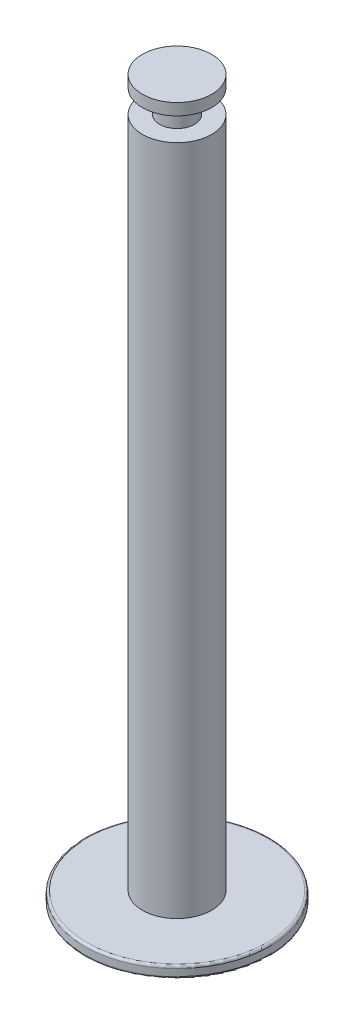
SolidWorks part; units mm, degrees
ref_plane "Front Plane" through (0, 0, 0) normal (0, 0, 1) x (1, 0, 0)
ref_plane "Top Plane" through (0, 0, 0) normal (0, 1, 0) x (1, 0, 0)
ref_plane "Right Plane" through (0, 0, 0) normal (1, 0, 0) x (0, 0, -1)
sketch "Sketch1" plane through (0, 0, 0) normal (0, 1, 0) x (1, 0, 0)
  circle A0 centre (0, 0) radius 7.99
extrude "Boss-Extrude1" add sketch "Sketch1" along normal blind 1
fillet "Fillet1" radius 0.2 2 edges at (0, 0, 7.99) (0, 1, 7.99)
sketch "Sketch2" plane through (0, 1, 0) normal (0, 1, 0) x (1, 0, 0)
  circle A0 centre (0, 0) radius 2.99
extrude "Boss-Extrude3" add sketch "Sketch2" along normal blind 58
sketch "Sketch4" plane through (0, 59, 0) normal (0, 1, 0) x (1, 0, 0)
  circle A0 centre (0, 0) radius 1.5
extrude "Boss-Extrude4" add sketch "Sketch4" along normal blind 2
sketch "Sketch5" plane through (0, 61, 0) normal (0, 1, 0) x (1, 0, 0)
  circle A0 centre (0, 0) radius 2.99
extrude "Boss-Extrude5" add sketch "Sketch5" along normal blind 1
ref_axis "Axis1" through (0, 76.995, 0) along (0, -1, 0)
